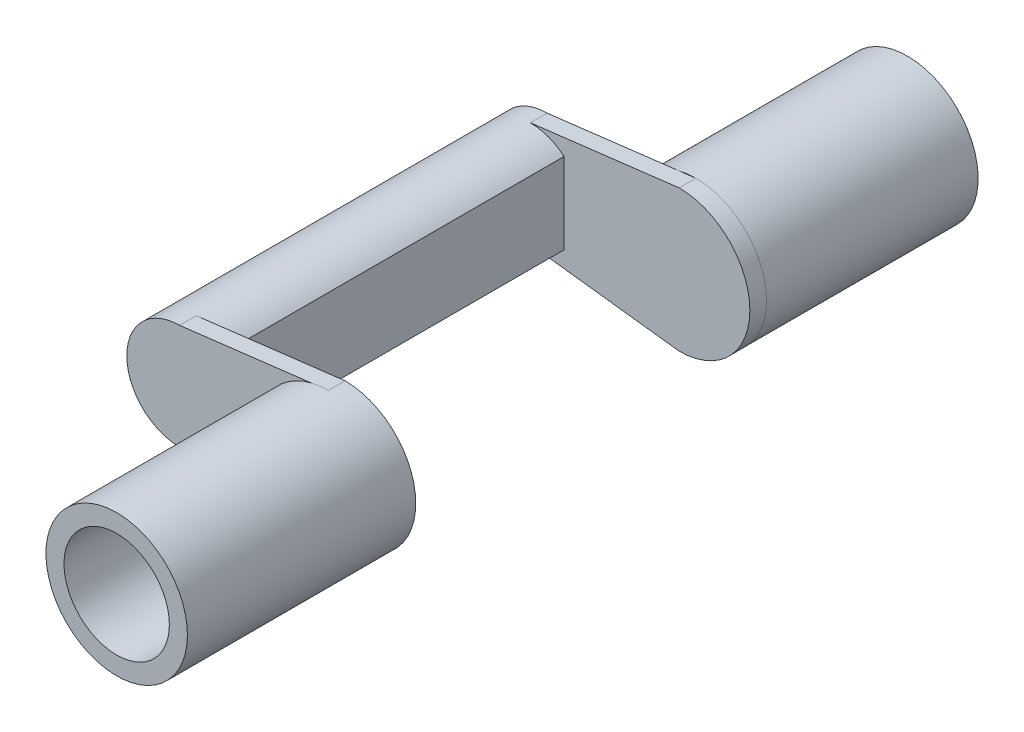
SolidWorks part; units mm, degrees
ref_plane "Front" through (0, 0, 0) normal (0, 0, 1) x (1, 0, 0)
ref_plane "Top" through (0, 0, 0) normal (0, 1, 0) x (1, 0, 0)
ref_plane "Right" through (0, 0, 0) normal (1, 0, 0) x (0, 0, -1)
sketch "Sketch4" plane through (0, 0, 0) normal (0, 0, 1) x (1, 0, 0)
  line L0 (0, -42.8625) -> (0, 41.275) construction
  line L1 (-49.15, -15.5) -> (-80.15, 15.5) construction
  line L2 (-80.15, -15.5) -> (-49.15, 15.5) construction
  line L3 (-39.925, 44.5615) -> (-39.925, -66.5635) construction
  line L4 (-71.275, 44.5615) -> (-71.275, -66.5635) construction
  line L8 (-62.05, 15.5) -> (-31.05, -15.5) construction
  line L9 (-31.05, 15.5) -> (-62.05, -15.5) construction
  line L11 (-31.05, 36.624) -> (-31.05, -53.8635) construction
  line L12 (43.75, 0) -> (-164.4633, 0) construction
  line L13 (-62.05, 36.624) -> (-62.05, -53.8635) construction
  line L14 (-49.15, 36.624) -> (-49.15, -53.8635) construction
  line L15 (-80.15, 36.624) -> (-80.15, -53.8635) construction
  line L16 (-113.2228, 15.5) -> (-0.2036, 15.5) construction
  line L17 (-113.2228, -15.5) -> (-0.2036, -15.5) construction
  line L18 (-25, -66.5635) -> (-25, 44.5615) construction
  line L19 (-68.1, -66.5635) -> (-68.1, 44.5615) construction
  line L20 (-43.1, 44.5615) -> (-43.1, -66.5635) construction
  line L21 (-86.2, -66.5635) -> (-86.2, 44.5615) construction
  line L22 (5.8397, -21.55) -> (-134.1626, -21.55) construction
  line L23 (5.8397, 21.55) -> (-134.1626, 21.55) construction
  line L24 (10.9249, -24.725) -> (-138.6228, -24.725) construction
  line L25 (10.9249, 24.725) -> (-138.6228, 24.725) construction
  line L26 (-89.375, 44.5615) -> (-89.375, -66.5635) construction
  line L27 (-21.825, 44.5615) -> (-21.825, -66.5635) construction
  circle A0 centre (0, 0) radius 12.7 construction
  circle A1 centre (0, 0) radius 15.875 construction
  circle A2 centre (0, 0) radius 9.46 construction
  circle A3 centre (-93.65, 0) radius 9.46 construction
  arc A4 (-93.65, 12.7) -> (-93.65, -12.7) centre (-93.65, 0) ccw construction
  circle A5 centre (27.27, 0) radius 9.46 construction
  circle A6 centre (27.27, 0) radius 12.7 construction
  circle A7 centre (-120.3675, 0) radius 9.46 construction
  circle A8 centre (-120.3675, 0) radius 12.7 construction
  point P3 (0, 0)
  point P6 (-49.15, -15.5)
  point P11 (-93.65, 0)
  point P12 (-49.15, 15.5)
  point P13 (-46.55, 0)
  point P14 (-80.15, 15.5)
  point P15 (-80.15, -15.5)
  point P61 (-64.65, 0)
  point P65 (27.27, 0)
  point P66 (-120.3675, 0)
  dimension "D20" = 3.175
  dimension "D18" = 29
  dimension "D26" = 73.82
  dimension "D27" = 64.65
  dimension "D2" = 31
  dimension "D3" = 25
  dimension "D4" = 31
  dimension "D5" = 21.825
  dimension "D6" = 15.5
  dimension "D7" = 15.5
  dimension "D8" = 6.05
  dimension "D9" = 6.05
  dimension "D10" = 6.05
  dimension "D11" = 6.05
  dimension "D12" = 6.05
  dimension "D13" = 6.05
  dimension "D14" = 3.175
  dimension "D15" = 3.175
  dimension "D16" = 3.175
  dimension "D17" = 3.175
  dimension "D19" = 3.175
  dimension "D21" = 3.175
  dimension "D22" = 46.55
  dimension "D23" = 47.1
  dimension "D24" = 58.32
  dimension "D25" = 147.6375
sketch "Sketch5" plane through (0, 0, 0) normal (0, 0, 1) x (1, 0, 0)
  circle A0 centre (-93.65, 0) radius 7.8
extrude "Extrude1" add sketch "Sketch5" against normal blind 10
sketch "Sketch6" plane through (0, 0, 0) normal (0, 0, 1) x (1, 0, 0)
  circle A0 centre (-93.65, 0) radius 12.6875
extrude "Extrude2" add sketch "Sketch6" along normal blind 3
sketch "Sketch7" plane through (0, 0, 0) normal (0, 0, -1) x (-1, 0, 0)
  circle A0 centre (93.65, 0) radius 12.6875
  circle A1 centre (93.65, 0) radius 9.46
extrude "Extrude3" add sketch "Sketch7" along normal blind 35
sketch "Sketch9" plane through (0, 0, 3) normal (0, 0, 1) x (1, 0, 0)
  line L1 (-93.65, -12.7) -> (-120.3675, -9.46)
  line L2 (-93.65, 12.7) -> (-120.3675, 9.46)
  circle A0 centre (-93.65, 0) radius 12.6875 construction
  arc A1 (-93.65, -12.7) -> (-93.65, 12.7) centre (-93.65, 0) ccw
  arc A2 (-120.3675, 9.46) -> (-120.3675, -9.46) centre (-120.3675, 0) ccw
  circle A4 centre (-120.3675, 0) radius 9.46 construction
extrude "Extrude5" add sketch "Sketch9" along normal blind 3
sketch "Sketch10" plane through (0, 0, 6) normal (0, 0, 1) x (1, 0, 0)
  line L0 (-114.3, -9.525) -> (-114.3, 17.4625) construction
  line L1 (-114.3, -7.2579) -> (-114.3, 7.2579)
  arc A0 (-114.3, 7.2579) -> (-114.3, -7.2579) centre (-120.3675, 0) ccw
  circle A1 centre (-120.3675, 0) radius 9.46 construction
  circle A2 centre (-120.3675, 0) radius 4.48
extrude "Extrude6" add sketch "Sketch10" along normal blind 60
sketch "Sketch11" plane through (0, 0, 66) normal (0, 0, 1) x (1, 0, 0)
  line L0 (-93.65, 12.7) -> (-120.3675, 9.46)
  line L1 (-93.65, -12.7) -> (-120.3675, -9.46)
  arc A0 (-120.3675, 9.46) -> (-120.3675, -9.46) centre (-120.3675, 0) ccw
  circle A1 centre (-120.3675, 0) radius 9.46 construction
  arc A2 (-93.65, 12.7) -> (-93.65, -12.7) centre (-93.65, 0) cw
  arc A3 (-93.65, -12.7) -> (-93.65, 12.7) centre (-93.65, 0) ccw construction
extrude "Extrude7" add sketch "Sketch11" along normal blind 3
sketch "Sketch12" plane through (0, 0, 69) normal (0, 0, 1) x (1, 0, 0)
  circle A0 centre (-93.65, 0) radius 7.7
extrude "Extrude8" add sketch "Sketch12" along normal blind 10
sketch "Sketch13" plane through (0, 0, 69) normal (0, 0, 1) x (1, 0, 0)
  circle A0 centre (-93.65, 0) radius 9.46
  circle A1 centre (-93.65, 0) radius 12.7
extrude "Extrude9" add sketch "Sketch13" along normal blind 38
